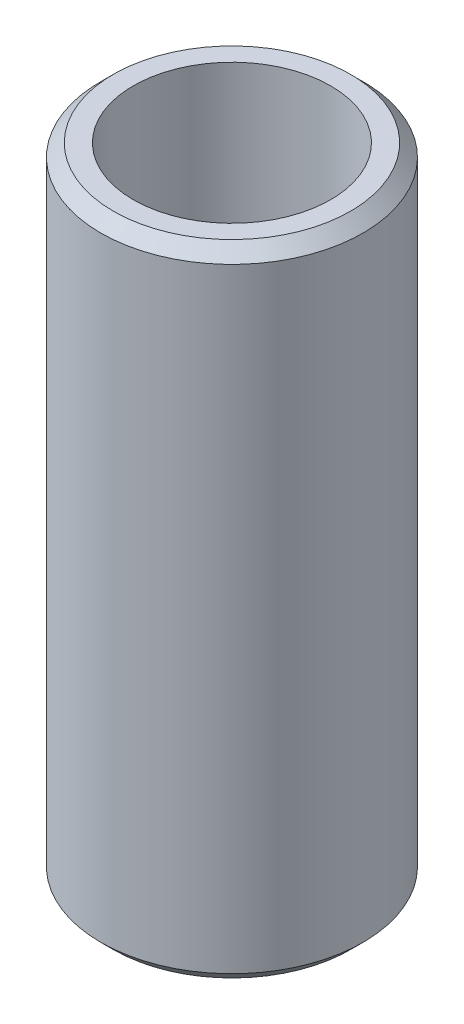
SolidWorks part; units mm, degrees
ref_plane "Front Plane" through (0, 0, 0) normal (0, 0, 1) x (1, 0, 0)
ref_plane "Top Plane" through (0, 0, 0) normal (0, 1, 0) x (1, 0, 0)
ref_plane "Right Plane" through (0, 0, 0) normal (1, 0, 0) x (0, 0, -1)
sketch "Sketch1" plane through (0, 0, 0) normal (0, 1, 0) x (1, 0, 0)
  circle A0 centre (0, 0) radius 57.5
  dimension "SHAFT_OD" = 115
extrude "Boss-Extrude1" add sketch "Sketch1" along normal blind 280.2986
sketch "Sketch2" plane through (0, 0, 0) normal (0, 1, 0) x (1, 0, 0)
  circle A0 centre (0, 0) radius 43.2547
  dimension "BORE_D" = 86.5095
extrude "Cut-Extrude1" cut sketch "Sketch2" along normal through all
chamfer "Chamfer1" distance 5.5213 angle 45 2 edges at (0, 280.2986, 57.5) (0, 0, 57.5)
